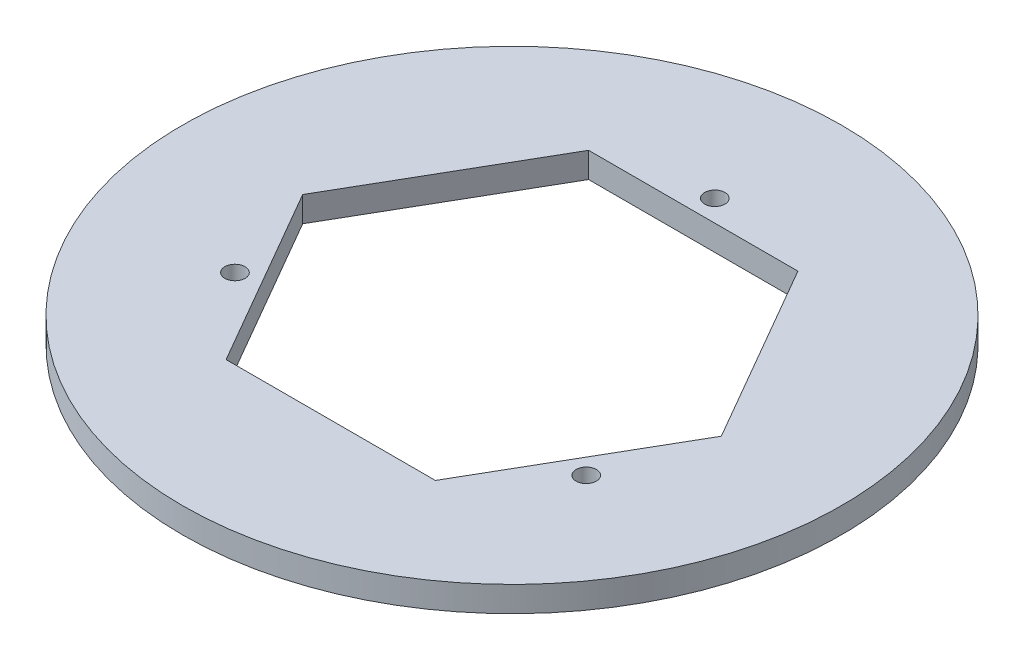
SolidWorks part; units mm, degrees
ref_plane "Ebene vorne" through (0, 0, 0) normal (0, 0, 1) x (1, 0, 0)
ref_plane "Ebene oben" through (0, 0, 0) normal (0, 1, 0) x (1, 0, 0)
ref_plane "Ebene rechts" through (0, 0, 0) normal (1, 0, 0) x (0, 0, -1)
sketch "Skizze1" plane through (0, 0, 0) normal (0, 1, 0) x (1, 0, 0)
  line L0 (0, 0) -> (41.2805, 0) construction
  line L1 (41.2805, 0) -> (20.6403, 35.75)
  line L2 (20.6403, 35.75) -> (-20.6403, 35.75)
  line L3 (-20.6403, 35.75) -> (-41.2805, 0)
  line L4 (-41.2805, 0) -> (-20.6403, -35.75)
  line L5 (-20.6403, -35.75) -> (20.6403, -35.75)
  line L6 (20.6403, -35.75) -> (41.2805, 0)
  line L7 (0, 0) -> (0, 40) construction
  circle A0 centre (0, 0) radius 35.75 construction
  circle A1 centre (0, 0) radius 65
  circle A2 centre (0, 40) radius 2
  circle A3 centre (34.641, -20) radius 2
  circle A4 centre (-34.641, -20) radius 2
  point P18 (0, 0)
  dimension "D1" = 71.5
  dimension "D2" = 130
  dimension "D3" = 4
  dimension "D4" = 40
  dimension "D5" = 3
extrude "Aufsatz-Linear austragen1" add sketch "Skizze1" along normal blind 5
